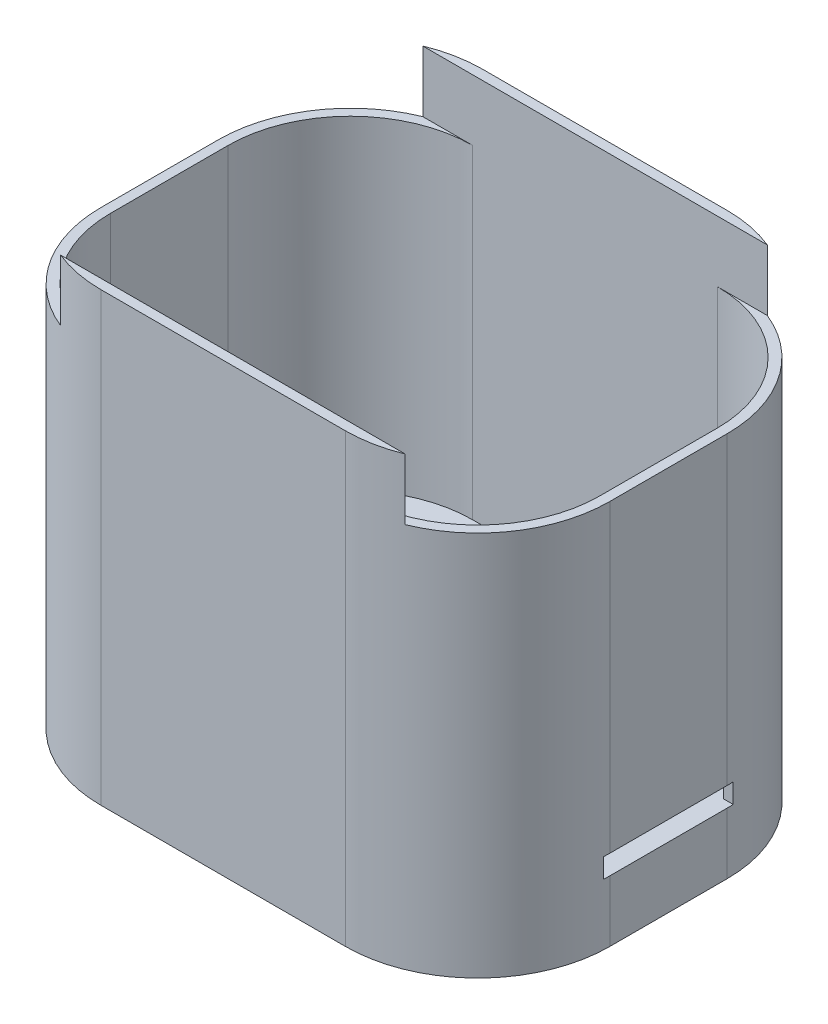
SolidWorks part; units mm, degrees
ref_plane "前基準面" through (0, 0, 0) normal (0, 0, 1) x (1, 0, 0)
ref_plane "上基準面" through (0, 0, 0) normal (0, 1, 0) x (1, 0, 0)
ref_plane "右基準面" through (0, 0, 0) normal (1, 0, 0) x (0, 0, -1)
sketch "草圖1" plane through (0, 0, 0) normal (0, 1, 0) x (1, 0, 0)
  line L0 (-10, -15.6) -> (10, -15.6)
  line L1 (-10, -14.8) -> (10, -14.8)
  line L2 (-20, -4.8) -> (-20, 4.8)
  line L3 (-10, 14.8) -> (10, 14.8)
  line L4 (20, -4.8) -> (20, 4.8)
  line L5 (-20, -14.8) -> (20, 14.8) construction
  line L6 (-20, 14.8) -> (20, -14.8) construction
  line L7 (20.8, -4.8) -> (20.8, 4.8)
  line L8 (-10, 15.6) -> (10, 15.6)
  line L9 (-20.8, -4.8) -> (-20.8, 4.8)
  arc A0 (-20, 4.8) -> (-10, 14.8) centre (-10, 4.8) cw
  arc A1 (10, 14.8) -> (20, 4.8) centre (10, 4.8) cw
  arc A2 (20, -4.8) -> (10, -14.8) centre (10, -4.8) cw
  arc A3 (-10, -14.8) -> (-20, -4.8) centre (-10, -4.8) cw
  arc A4 (20.8, -4.8) -> (10, -15.6) centre (10, -4.8) cw
  arc A5 (10, 15.6) -> (20.8, 4.8) centre (10, 4.8) cw
  arc A6 (-20.8, 4.8) -> (-10, 15.6) centre (-10, 4.8) cw
  arc A7 (-10, -15.6) -> (-20.8, -4.8) centre (-10, -4.8) cw
  point P0 (0, 0)
  dimension "D3" = 10
  dimension "D4" = 10
  dimension "D1" = 40
  dimension "D2" = 29.6
  dimension "D5" = 0.8
extrude "填料-伸長1" add sketch "草圖1" along normal blind 36.5
sketch "草圖4" plane through (0, 36.5, 0) normal (0, 1, 0) x (1, 0, 0)
  line L0 (10, 14.8) -> (-10, 14.8) construction
  line L1 (-20.8, -14.8) -> (20.8, -14.8)
  line L2 (-20.8, -14.8) -> (-20.8, 14.8)
  line L3 (-20.8, 14.8) -> (20.8, 14.8)
  line L4 (20.8, -14.8) -> (20.8, 14.8)
  line L5 (-20.8, -14.8) -> (20.8, 14.8) construction
  line L6 (-20.8, 14.8) -> (20.8, -14.8) construction
  line L8 (-20.8, 4.8) -> (-20.8, -4.8) construction
  point P0 (0, 0)
  point P8 (-20.8, 0)
extrude "除料-伸長1" cut sketch "草圖4" against normal blind 5
sketch "草圖5" plane through (0, 0, 0) normal (0, -1, 0) x (1, 0, 0)
  line L0 (20, 4.8) -> (20, -4.8) construction
  line L1 (-10, 14.8) -> (10, 14.8) construction
  line L2 (10, -14.8) -> (-10, -14.8) construction
  line L3 (-20, -4.8) -> (-20, 4.8) construction
  line L4 (20, 4.8) -> (20, -4.8)
  line L5 (-10, 14.8) -> (10, 14.8)
  line L6 (10, -14.8) -> (-10, -14.8)
  line L7 (-20, -4.8) -> (-20, 4.8)
  arc A0 (20, 4.8) -> (10, 14.8) centre (10, 4.8) ccw construction
  arc A1 (10, -14.8) -> (20, -4.8) centre (10, -4.8) ccw construction
  arc A2 (-20, -4.8) -> (-10, -14.8) centre (-10, -4.8) ccw construction
  arc A3 (-10, 14.8) -> (-20, 4.8) centre (-10, 4.8) ccw construction
  arc A4 (20, 4.8) -> (10, 14.8) centre (10, 4.8) ccw
  arc A5 (10, -14.8) -> (20, -4.8) centre (10, -4.8) ccw
  arc A6 (-20, -4.8) -> (-10, -14.8) centre (-10, -4.8) ccw
  arc A7 (-10, 14.8) -> (-20, 4.8) centre (-10, 4.8) ccw
extrude "填料-伸長2" add sketch "草圖5" against normal blind 5
sketch "草圖6" plane through (20.8, 0, 0) normal (1, 0, 0) x (0, 0, -1)
  line L0 (0, 0) -> (0, 28.7472) construction
  line L1 (-4.8, 31.5) -> (4.8, 31.5) construction
  line L3 (-5.3, 5) -> (5.3, 5)
  line L6 (-5.3, 5) -> (-5.3, 6.6)
  line L7 (-5.3, 6.6) -> (5.3, 6.6)
  line L8 (5.3, 6.6) -> (5.3, 5)
  dimension "D1" = 10.6
  dimension "D2" = 1.6
  dimension "D3" = 26.5
extrude "除料-伸長2" cut sketch "草圖6" against normal through all
sketch "草圖7" plane through (0, 0, 0) normal (0, -1, 0) x (1, 0, 0)
  line L0 (12, 2.6946) -> (12, 22.5997) construction
  line L1 (12, 0) -> (-49988, 0) construction
  line L2 (-12, 0) -> (-12, 17.5104) construction
  line L3 (-20.8, -4.8) -> (-20.8, 4.8) construction
  circle A0 centre (-12, 3.8) radius 1.3
  circle A1 centre (-4, 3.8) radius 1.3
  circle A2 centre (4, 3.8) radius 1.3
  circle A3 centre (12, 3.8) radius 1.3
  circle A7 centre (12, -3.8) radius 1.3
  circle A8 centre (4, -3.8) radius 1.3
  circle A9 centre (-4, -3.8) radius 1.3
  circle A10 centre (-12, -3.8) radius 1.3
  point P11 (-20.8, 0)
  dimension "D2" = 2.6
  dimension "D3" = 7.6
  dimension "D14" = 4
extrude "除料-伸長3" cut sketch "草圖7" against normal through all
